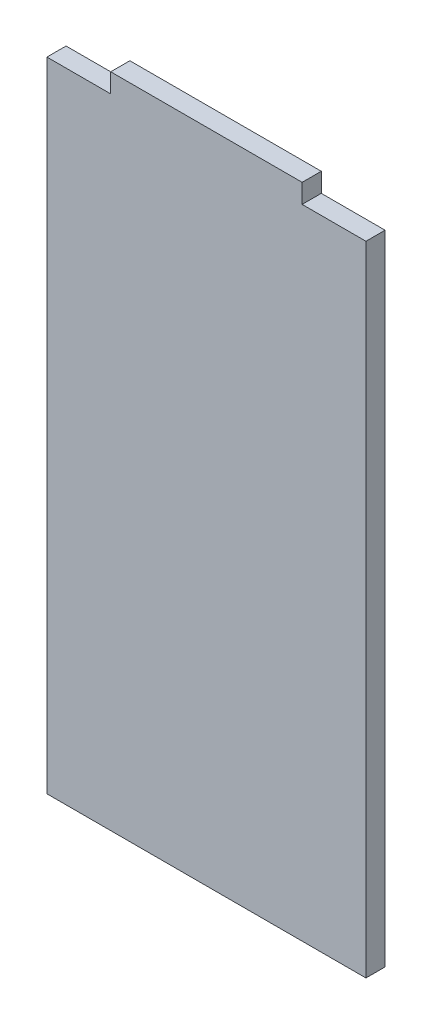
SolidWorks part; units mm, degrees
material "ABS"
ref_plane "Спереди" through (0, 0, 0) normal (0, 0, 1) x (1, 0, 0)
ref_plane "Сверху" through (0, 0, 0) normal (0, 1, 0) x (1, 0, 0)
ref_plane "Справа" through (0, 0, 0) normal (1, 0, 0) x (0, 0, -1)
sketch "Эскиз1" plane through (0, 0, 0) normal (0, 0, 1) x (1, 0, 0)
  line L1 (-25, -50) -> (25, -50)
  line L2 (-25, -50) -> (-25, 50)
  line L3 (-25, 50) -> (25, 50)
  line L4 (25, -50) -> (25, 50)
  line L5 (-25, -50) -> (25, 50) construction
  line L6 (-25, 50) -> (25, -50) construction
  line L7 (-15, 47) -> (15, 47)
  line L8 (-15, 47) -> (-15, 53)
  line L9 (-15, 53) -> (15, 53)
  line L10 (15, 47) -> (15, 53)
  line L11 (-15, 47) -> (15, 53) construction
  line L12 (-15, 53) -> (15, 47) construction
  point P0 (0, 0)
  point P6 (0, 50)
  dimension "D1" = 3
  dimension "D2" = 30
  dimension "D3" = 10
  dimension "D4" = 100
extrude "Бобышка-Вытянуть1" add sketch "Эскиз1" along normal blind 3 contours L10 L7 L8 L3 L2 L1 L4 | L7 L10 L3 L8 | L3 L10 L9 L8 region at (0, -0.889, 0) region at (0, 51.5, 0) region at (0, 48.5, 0)
